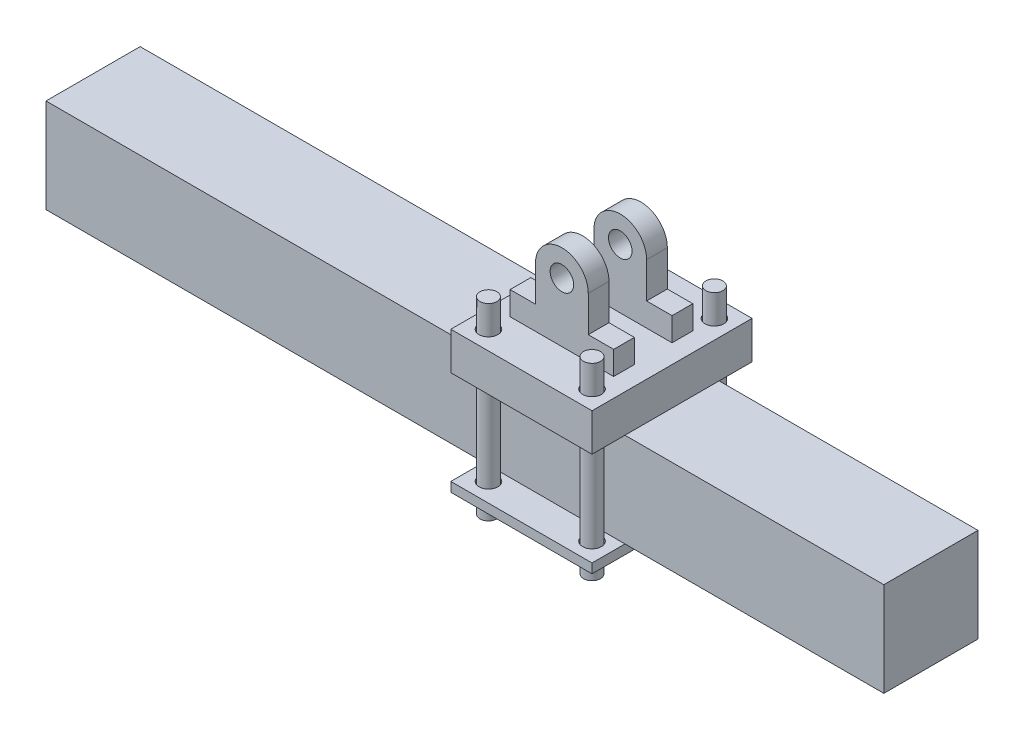
SolidWorks part; units mm, degrees
material "Plain Carbon Steel"
ref_plane "Front Plane" through (0, 0, 0) normal (0, 0, 1) x (1, 0, 0)
ref_plane "Top Plane" through (0, 0, 0) normal (0, 1, 0) x (1, 0, 0)
ref_plane "Right Plane" through (0, 0, 0) normal (1, 0, 0) x (0, 0, -1)
ref_plane "Plane1" through (0, 0, 20) normal (0, 0, 1) x (1, 0, 0)
sketch "Sketch2" plane through (0, 0, 0) normal (0, 0, 1) x (1, 0, 0)
  line L1 (0, 0) -> (850, 0)
  line L2 (0, 0) -> (0, 100)
  line L3 (0, 100) -> (850, 100)
  line L4 (850, 0) -> (850, 100)
  dimension "D1" = 850
  dimension "D2" = 100
extrude "Boss-Extrude1" add sketch "Sketch2" along normal mid plane 100
sketch "Sketch7" plane through (0, 0, 0) normal (0, 0, 1) x (1, 0, 0)
  line L8 (5, 95) -> (5, 5)
  line L9 (845, 95) -> (5, 95)
  line L10 (845, 5) -> (845, 95)
  line L11 (5, 5) -> (845, 5)
  line L12 (5, 95) -> (5, 5)
  line L13 (845, 95) -> (5, 95)
  line L14 (845, 5) -> (845, 95)
  line L15 (5, 5) -> (845, 5)
  dimension "D1" = 5
extrude "Cut-Extrude2" cut sketch "Sketch7" against normal mid plane 90
sketch "Sketch8" plane through (0, 0, 0) normal (0, 0, 1) x (1, 0, 0)
  line L0 (850, 100) -> (0, 100) construction
  line L1 (45, 100) -> (195, 100)
  line L2 (45, 100) -> (45, 110)
  line L3 (45, 110) -> (195, 110)
  line L4 (195, 100) -> (195, 110)
  line L5 (0, 0) -> (850, 0) construction
  line L6 (45, 0) -> (195, 0)
  line L7 (45, 0) -> (45, -10)
  line L8 (45, -10) -> (195, -10)
  line L9 (195, 0) -> (195, -10)
  line L10 (120, 110) -> (120, -10) construction
  dimension "D1" = 150
  dimension "D2" = 10
  dimension "D3" = 10
  dimension "D4" = 120
extrude "Boss-Extrude6" [suppressed] add sketch "Sketch8" along normal mid plane 170
sketch "Sketch11" plane through (0, 0, 0) normal (0, 0, 1) x (1, 0, 0)
  line L1 (25, 100) -> (175, 100)
  line L2 (25, 100) -> (25, 110)
  line L3 (25, 110) -> (175, 110)
  line L4 (175, 100) -> (175, 110)
  line L6 (25, 0) -> (175, 0)
  line L7 (25, 0) -> (25, -10)
  line L8 (25, -10) -> (175, -10)
  line L9 (175, 0) -> (175, -10)
  line L10 (100, 110) -> (100, -10) construction
  dimension "D1" = 150
  dimension "D2" = 10
  dimension "D3" = 10
  dimension "D4" = 100
sketch "Sketch12" plane through (0, 0, 0) normal (0, 0, 1) x (1, 0, 0)
  line L0 (850, 100) -> (0, 100) construction
  line L1 (425, 100) -> (575, 100)
  line L2 (425, 100) -> (425, 140)
  line L3 (425, 140) -> (575, 140)
  line L4 (575, 100) -> (575, 140)
  line L6 (425, 0) -> (575, 0)
  line L7 (425, 0) -> (425, -10)
  line L8 (425, -10) -> (575, -10)
  line L9 (575, 0) -> (575, -10)
  line L10 (500, 140) -> (500, -10) construction
  dimension "D1" = 150
  dimension "D2" = 40
  dimension "D3" = 10
  dimension "D4" = 500
extrude "Boss-Extrude8" [suppressed] add sketch "Sketch11" along normal mid plane 170
extrude "Boss-Extrude9" add sketch "Sketch12" along normal mid plane 170
sketch "Sketch9" [suppressed] plane through (0, 0, 0) normal (0, 1, 0) x (1, 0, 0)
  line L0 (0, 0) -> (444.8159, 0) construction
  line L1 (175, 65) -> (175, 0) construction
  line L2 (65, 65) -> (65, 0) construction
  line L3 (45, -85) -> (45, 85) construction
  line L4 (195, 85) -> (45, 85) construction
  line L5 (195, -85) -> (195, 85) construction
  circle A0 centre (175, 65) radius 10
  circle A1 centre (65, 65) radius 10
  circle A2 centre (65, -65) radius 10
  circle A3 centre (175, -65) radius 10
  dimension "D1" = 20
  dimension "D2" = 20
  dimension "D3" = 20
  dimension "D4" = 20
  dimension "D5" = 20
extrude "Cut-Extrude3 (pos 1&2)" [suppressed] cut sketch "Sketch9" against normal blind 160 and the other way blind 160
sketch "Sketch10" [suppressed] plane through (0, 0, 0) normal (0, 1, 0) x (1, 0, 0)
  line L0 (45, 0) -> (195, 0) construction
  line L1 (175, 65) -> (65, 65) construction
  line L2 (175, 65) -> (175, -65) construction
  line L3 (175, -65) -> (65, -65) construction
  line L4 (65, 65) -> (65, -65) construction
  line L5 (45, -85) -> (45, 85) construction
  line L6 (195, -85) -> (195, 85) construction
  circle A0 centre (175, 65) radius 9
  circle A1 centre (65, 65) radius 9
  circle A2 centre (65, -65) radius 9
  circle A3 centre (175, -65) radius 9
  dimension "D1" = 18
extrude "Boss-Extrude7 (pos 1&2)" [suppressed] add sketch "Sketch10" along normal blind 120 and the other way blind 20 separate body
sketch "Sketch3" plane through (0, 0, 20) normal (0, 0, 1) x (1, 0, 0)
  line L0 (120, 110) -> (120, 57.6289) construction
  line L1 (195, 110) -> (45, 110) construction
  line L2 (870.2621, 110) -> (-104.8876, 110) construction
  line B0 (175, 110) -> (175, 135)
  line B1 (65, 110) -> (65, 135)
  line B2 (92, 135) -> (92, 173)
  line B3 (148, 135) -> (148, 173)
  arc B4 (92, 173) -> (148, 173) centre (120, 173) cw
  circle B5 centre (120, 173) radius 12.5
  line B6 (65, 135) -> (92, 135)
  line B7 (148, 135) -> (175, 135)
  line B8 (65, 110) -> (175, 110)
sketch_block_instance "Block1-2"
sketch_block "Block1" parameters "D3"=28, "D4"=25, "D1"=25, "D2"=110, "D5"=38, "D6"=35.7168
extrude "Boss-Extrude2 (pos 1&2)" [suppressed] add sketch "Sketch3" along normal blind 22
ref_plane "Plane2" through (0, 173, 0) normal (0, 1, 0) x (1, 0, 0)
sketch "Sketch5" plane through (0, 0, 0) normal (-1, 0, 0) x (0, 0, 1)
  line L1 (-50, 0) -> (50, 0)
  line L2 (-50, 0) -> (-50, 100)
  line L3 (-50, 100) -> (50, 100)
  line L4 (50, 0) -> (50, 100)
extrude "Boss-Extrude4" add sketch "Sketch5" along normal blind 40
mirror "Mirror1" [suppressed] about plane through (0, 0, 0) normal (0, 0, 1)
sketch "Sketch13" plane through (0, 0, 0) normal (0, 1, 0) x (1, 0, 0)
  line L0 (0, 0) -> (575, 0) construction
  line L1 (555, 65) -> (555, 0) construction
  line L2 (445, 65) -> (445, 0) construction
  line L6 (575, 85) -> (425, 85) construction
  line L7 (425, -85) -> (425, 85) construction
  line L8 (575, -85) -> (575, 85) construction
  line L9 (575, 50) -> (575, 85) construction
  circle A0 centre (555, 65) radius 10
  circle A1 centre (445, 65) radius 10
  circle A2 centre (445, -65) radius 10
  circle A3 centre (555, -65) radius 10
  dimension "D1" = 20
  dimension "D2" = 20
  dimension "D3" = 20
  dimension "D4" = 20
  dimension "D5" = 20
extrude "Cut-Extrude3" cut sketch "Sketch13" against normal through all and the other way through all
sketch "Sketch14" plane through (0, 0, 0) normal (0, 1, 0) x (1, 0, 0)
  line L0 (425, 0) -> (575, 0) construction
  line L1 (555, 65) -> (445, 65) construction
  line L2 (555, 65) -> (555, -65) construction
  line L3 (555, -65) -> (445, -65) construction
  line L4 (445, 65) -> (445, -65) construction
  line L7 (575, -85) -> (575, 85) construction
  line L8 (425, -85) -> (425, 85) construction
  circle A0 centre (555, 65) radius 9
  circle A1 centre (445, 65) radius 9
  circle A2 centre (445, -65) radius 9
  circle A3 centre (555, -65) radius 9
  circle A4 centre (445, 65) radius 10 construction
  circle A5 centre (555, 65) radius 10 construction
  dimension "D1" = 18
extrude "Boss-Extrude10" add sketch "Sketch14" along normal blind 170 and the other way blind 30 separate body
sketch "Sketch15" plane through (0, 0, 20) normal (0, 0, 1) x (1, 0, 0)
  line L0 (575, 140) -> (425, 140) construction
  line L1 (575, 140) -> (425, 140) construction
  line L2 (500, 140) -> (500, 92.1416) construction
  line B0 (555, 140) -> (555, 165)
  line B1 (445, 140) -> (445, 165)
  line B2 (472, 165) -> (472, 203)
  line B3 (528, 165) -> (528, 203)
  arc B4 (472, 203) -> (528, 203) centre (500, 203) cw
  circle B5 centre (500, 203) radius 12.5
  line B6 (445, 165) -> (472, 165)
  line B7 (528, 165) -> (555, 165)
  line B8 (445, 140) -> (555, 140)
sketch_block_instance "Mounting_block-1"
extrude "Boss-Extrude11" add sketch "Sketch15" along normal blind 22
mirror "Mirror2" about plane through (0, 0, 0) normal (0, 0, 1) of "Boss-Extrude11"
ref_plane "Plane3" through (0, 213, 0) normal (0, 1, 0) x (1, 0, 0)
